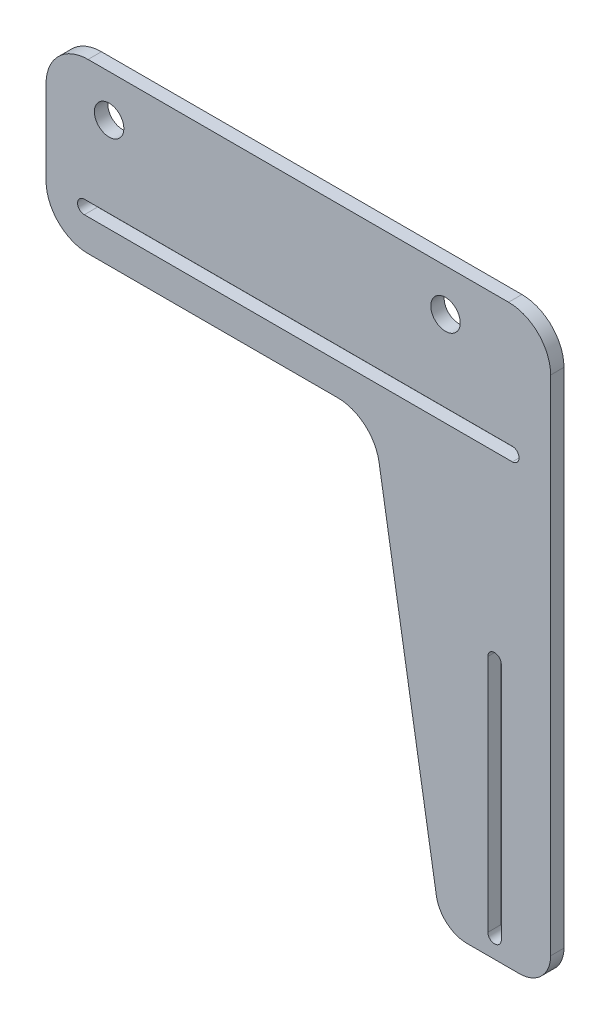
SolidWorks part; units mm, degrees
ref_plane "Front Plane" through (0, 0, 0) normal (0, 0, 1) x (1, 0, 0)
ref_plane "Top Plane" through (0, 0, 0) normal (0, 1, 0) x (1, 0, 0)
ref_plane "Right Plane" through (0, 0, 0) normal (1, 0, 0) x (0, 0, -1)
ref_plane "Plane1" through (0, 0, 3.175) normal (0, 0, 1) x (1, 0, 0)
sketch "Sketch11" plane through (0, 0, 3.175) normal (0, 0, 1) x (1, 0, 0)
  line L0 (40.1326, -82.0177) -> (52.6, -82.0177)
  line L1 (60, -74.6177) -> (60, 45)
  line L2 (50, 55) -> (-50, 55)
  line L3 (-60, 45) -> (-60, 25)
  line L4 (-50, 15) -> (9.3344, 15)
  line L5 (19.2005, 6.631) -> (32.8317, -75.8246)
  arc A0 (32.8317, -75.8246) -> (40.1326, -82.0177) centre (40.1326, -74.6177) ccw
  arc A1 (52.6, -82.0177) -> (60, -74.6177) centre (52.6, -74.6177) ccw
  arc A2 (60, 45) -> (50, 55) centre (50, 45) ccw
  arc A3 (-50, 55) -> (-60, 45) centre (-50, 45) ccw
  arc A4 (-60, 25) -> (-50, 15) centre (-50, 25) ccw
  arc A5 (9.3344, 15) -> (19.2005, 6.631) centre (9.3344, 5) cw
base flange "Base-Flange1" sketch "Sketch11" thickness 3.175 reverse thickness direction yes parameters "D1"=0
sketch "Sketch16" plane through (0, 0, 3.175) normal (0, 0, 1) x (1, 0, 0)
  line L0 (45.0718, -20.43) -> (45.0718, -77.23)
  line L1 (48.2718, -77.23) -> (48.2718, -20.43)
  arc A0 (45.0718, -77.23) -> (48.2718, -77.23) centre (46.6718, -77.23) ccw
  arc A1 (48.2718, -20.43) -> (45.0718, -20.43) centre (46.6718, -20.43) ccw
extrude "Cut-Extrude1" cut sketch "Sketch16" against normal through all
sketch "Sketch17" plane through (0, 0, 0) normal (0, 0, -1) x (-1, 0, 0)
  line L0 (50.9, 25.77) -> (-50.9, 25.77)
  line L1 (-50.9, 22.57) -> (50.9, 22.57)
  arc A0 (-50.9, 25.77) -> (-50.9, 22.57) centre (-50.9, 24.17) ccw
  arc A1 (50.9, 22.57) -> (50.9, 25.77) centre (50.9, 24.17) ccw
extrude "Cut-Extrude2" cut sketch "Sketch17" against normal through all
hole_wizard "Ø7.0 (7) Diameter Hole1" positions "Sketch19" profile "Sketch18" hole size "Ø7.0" standard "ANSI Metric"
sketch "Sketch19" plane through (0, 0, 3.175) normal (0, 0, 1) x (1, 0, 0)
  point P0 (35, 45)
  point P1 (-45, 45)
sketch "Sketch18" plane through (35, 45, 3.175) normal (1, 0, 0) x (0, -1, 0)
  line L0 (0, 0) -> (0, 3.175)
  line L1 (0, 3.175) -> (3.5, 3.175)
  line L2 (3.5, 3.175) -> (3.5, 0)
  line L5 (3.5, 0) -> (0, 0)
  line L11 (0, -6.35) -> (0, 107.95) construction
  dimension "Thru Hole Dia." = 7
  dimension "Thru Hole Depth" = 3.175
ref_point "Point1"
ref_point "Point2"
ref_plane "Plane2" through (0, 45, 0) normal (0, -1, 0) x (-1, 0, 0)
ref_plane "Plane3" through (0, 24.17, 0) normal (0, 1, 0) x (1, 0, 0)
ref_plane "Plane4" through (46.6718, 0, 0) normal (1, 0, 0) x (0, 0, -1)
sketch "Bend-Lines4" plane through (0, 0, 0) normal (0, 1, 0) x (1, 0, 0)
sketch "Bounding-Box4" plane through (0, 0, 0) normal (0, 1, 0) x (1, 0, 0)
sheet metal parameters "Sheet-Metal(6)" thickness 3.175 parameters "D1"=0
flat pattern "Flat-Pattern(6)" [suppressed]
sketch "Bend-Lines5" plane through (0, 0, 0) normal (0, 1, 0) x (1, 0, 0)
sketch "Bounding-Box5" [suppressed] plane through (0, 0, 0) normal (0, 1, 0) x (1, 0, 0)
sheet metal parameters "Sheet-Metal(7)" thickness 3.175 parameters "D1"=0
flat pattern "Flat-Pattern(6)"
sketch "Bend-Lines5" plane through (0, 0, 0) normal (0, 1, 0) x (1, 0, 0)
sketch "Bounding-Box5" [suppressed] plane through (0, 0, 0) normal (0, 1, 0) x (1, 0, 0)
sheet metal parameters "Sheet-Metal(8)" thickness 3.175 parameters "D1"=0
flat pattern "Flat-Pattern(6)"
sketch "Bend-Lines5" plane through (0, 0, 0) normal (0, 1, 0) x (1, 0, 0)
sketch "Bounding-Box5" [suppressed] plane through (0, 0, 0) normal (0, 1, 0) x (1, 0, 0)
sheet metal parameters "Sheet-Metal(9)" thickness 3.175 parameters "D1"=0
flat pattern "Flat-Pattern(6)"
sketch "Bend-Lines5" plane through (0, 0, 0) normal (0, 1, 0) x (1, 0, 0)
sketch "Bounding-Box5" [suppressed] plane through (0, 0, 0) normal (0, 1, 0) x (1, 0, 0)
